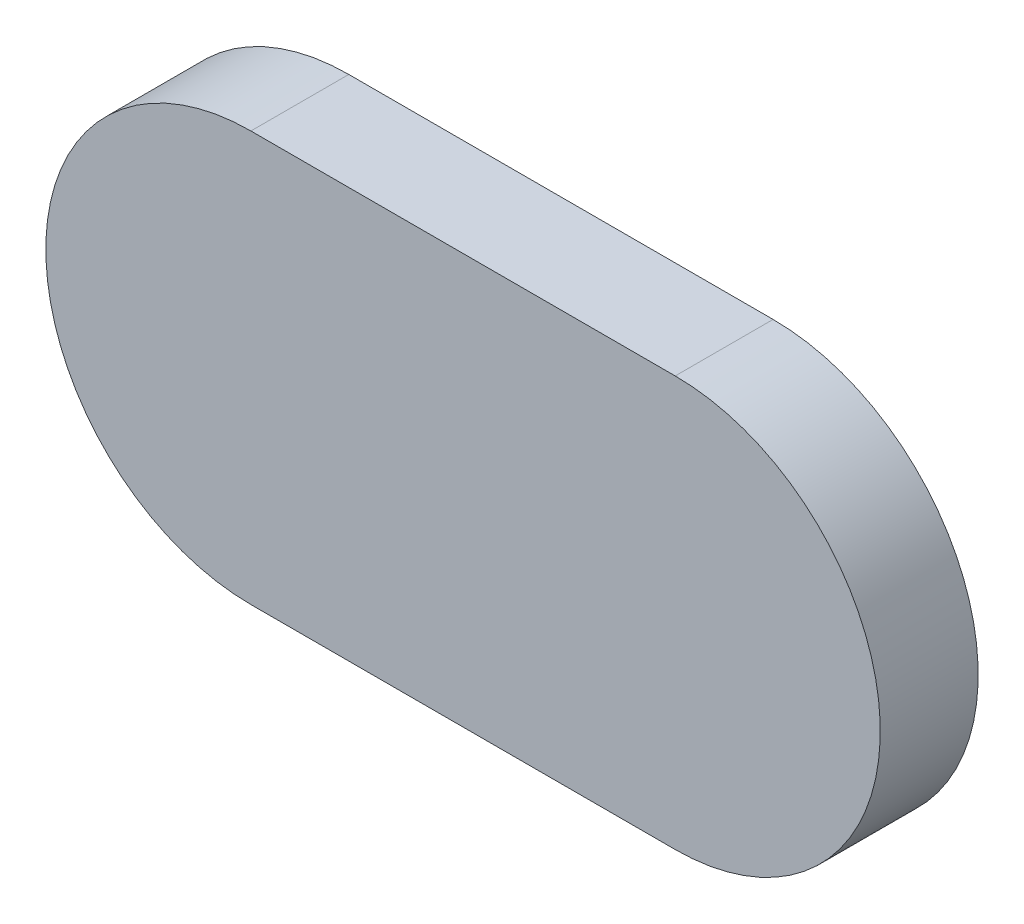
SolidWorks part; units mm, degrees
ref_plane "Plan de face" through (0, 0, 0) normal (0, 0, 1) x (1, 0, 0)
ref_plane "Plan de dessus" through (0, 0, 0) normal (0, 1, 0) x (1, 0, 0)
ref_plane "Plan de droite" through (0, 0, 0) normal (1, 0, 0) x (0, 0, -1)
sketch "Esquisse1" plane through (0, 0, 0) normal (0, 0, 1) x (1, 0, 0)
  line L9 (-75, -71.5957) -> (75, -71.5957)
  line L10 (-75, -71.5957) -> (-75, 73.4043)
  line L11 (-75, 73.4043) -> (75, 73.4043)
  line L12 (75, -71.5957) -> (75, 73.4043)
  line L14 (-75, -69.0957) -> (-75, 70.9043)
  line L16 (75, -69.0957) -> (75, 70.9043)
  circle A0 centre (-75, 0.9043) radius 72.5
  circle A1 centre (75, 0.9043) radius 72.5
  point P0 (0, 0)
  point P24 (-150, -72.5)
  point P25 (-150, -72.5)
  dimension "D1" = 75
  dimension "D2" = 75
extrude "Boss.-Extru.1" add sketch "Esquisse1" along normal blind 38 rebuild error yes
extrude "Boss.-Extru.2" add sketch "Esquisse1<2>" along normal blind 8 rebuild error yes
sketch "Esquisse1<2>" plane through (0, 0, 0) normal (0, 0, 1) x (1, 0, 0) same geometry as "Esquisse1"
sketch "Esquisse4" plane through (0, 0, 8) normal (0, 0, 1) x (1, 0, 0)
  line L1 (-5, 10) -> (5, 10)
  line L2 (-5, 10) -> (-5, -10)
  line L3 (-5, -10) -> (5, -10)
  line L4 (5, 10) -> (5, -10)
  point P5 (5, 0)
  dimension "D1" = 10
  dimension "D2" = 5
  dimension "D3" = 20
  dimension "D4" = 10
extrude "Enlèv. mat.-Extru.1" cut sketch "Esquisse4" against normal blind 8 rebuild error yes
sketch "Esquisse5" plane through (150, 0, 0) normal (1, 0, 0) x (0, 0, -1)
  circle A0 centre (-18.6426, 1.3477) radius 4.1583
extrude "Enlèv. mat.-Extru.2" cut sketch "Esquisse5" against normal blind 20 rebuild error yes
extrude "Boss.-Extru.3" add sketch "Esquisse1<3>" along normal blind 34.6094 separate body contours A0 | A1 | L9 L12 L11 L10
sketch "Esquisse1<3>" plane through (0, 0, 0) normal (0, 0, 1) x (1, 0, 0) same geometry as "Esquisse1"
extrude "Enlèv. mat.-Extru.3" cut sketch "Esquisse1<4>" along normal blind 19 rebuild error yes
sketch "Esquisse1<4>" plane through (0, 0, 0) normal (0, 0, 1) x (1, 0, 0) same geometry as "Esquisse1"
extrude "Enlèv. mat.-Extru.4" cut sketch "Esquisse1<7>" along normal blind 23 rebuild error yes
sketch "Esquisse1<7>" plane through (0, 0, 0) normal (0, 0, 1) x (1, 0, 0) same geometry as "Esquisse1"
extrude "Boss.-Extru.4" add sketch "Esquisse1<8>" along normal blind 4 rebuild error yes
sketch "Esquisse1<8>" plane through (0, 0, 0) normal (0, 0, 1) x (1, 0, 0) same geometry as "Esquisse1"
extrude "Enlèv. mat.-Extru.6" cut sketch "Esquisse1<10>" along normal blind 19 rebuild error yes
sketch "Esquisse1<10>" plane through (0, 0, 0) normal (0, 0, 1) x (1, 0, 0) same geometry as "Esquisse1"
